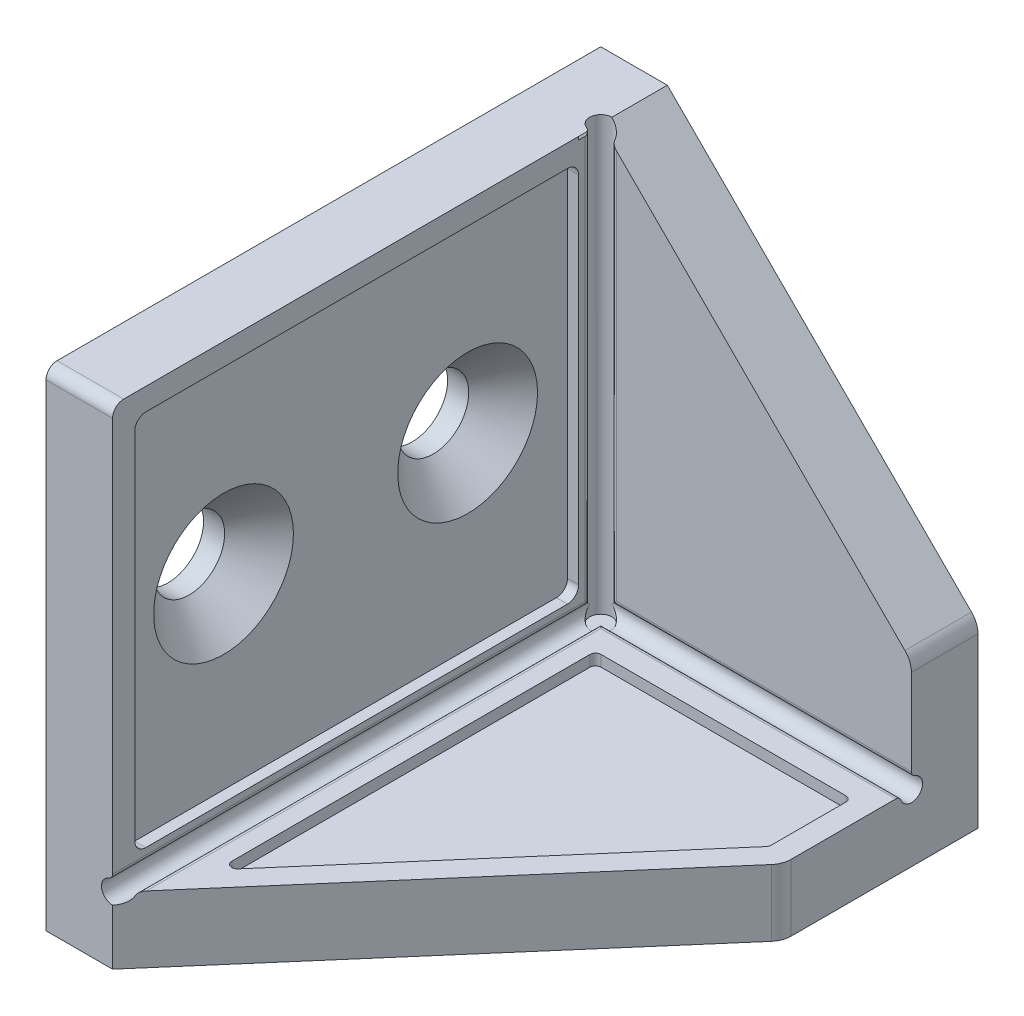
SolidWorks part; units mm, degrees
material "Polyester Resin"
ref_plane "Front Plane" through (0, 0, 0) normal (0, 0, 1) x (1, 0, 0)
ref_plane "Top Plane" through (0, 0, 0) normal (0, 1, 0) x (1, 0, 0)
ref_plane "Right Plane" through (0, 0, 0) normal (1, 0, 0) x (0, 0, -1)
sketch "Sketch1" plane through (0, 0, 0) normal (0, 0, 1) x (1, 0, 0)
  line L0 (0, 24.3075) -> (0, -0.6925)
  line L1 (0, -0.6925) -> (25, -0.6925)
  line L2 (0, 24.3075) -> (25, -0.6925)
  dimension "D1" = 25
  dimension "D2" = 25
extrude "Boss-Extrude2" add sketch "Sketch1" along normal blind 25
sketch "Sketch2" plane through (0, 0, 25) normal (0, 0, 1) x (1, 0, 0)
  line L0 (3, 21.3075) -> (3, 2.3075)
  line L1 (25, -0.6925) -> (0, 24.3075) construction
  line L2 (3, 2.3075) -> (22, 2.3075)
  line L3 (0, 24.3075) -> (0, -0.6925) construction
  line L4 (0, -0.6925) -> (25, -0.6925) construction
  line L5 (3, 21.3075) -> (22, 2.3075)
  dimension "D1" = 3
  dimension "D2" = 3
extrude "Cut-Extrude1" cut sketch "Sketch2" against normal blind 21
sketch "Sketch3" plane through (12.1537, 12.1537, 0) normal (0.7071, 0.7071, 0) x (0.7071, -0.7071, 0)
  line L0 (-12.9453, -4) -> (13.9247, -4)
  line L4 (13.9247, -4) -> (13.9247, -3)
  line L5 (13.9247, -3) -> (-12.9453, -3)
  line L6 (-12.9453, -3) -> (-12.9453, -4)
extrude "Cut-Extrude3" cut sketch "Sketch3" against normal blind 0.1
sketch "Sketch4" plane through (0, 0, 4) normal (0, 0, 1) x (1, 0, 0)
  line L0 (3, 21.3075) -> (3, 2.3075)
  line L1 (3, 2.3075) -> (22, 2.3075)
  line L2 (22, 2.3075) -> (3, 21.3075)
extrude "Cut-Extrude4" cut sketch "Sketch4" against normal up to surface (1 mm away) up to face at (12.4646, 11.7721, 3)
sketch "Sketch5" plane through (0, 0, 3) normal (0, 0, 1) x (1, 0, 0)
  line L0 (22, 2.3075) -> (21.8586, 2.3075)
  line L1 (21.8586, 2.3075) -> (21.9293, 2.2368)
  line L2 (21.9293, 2.2368) -> (22, 2.3075)
extrude "Boss-Extrude3" add sketch "Sketch5" along normal up to surface (1 mm away) up to face at (21.9293, 2.2839, 4)
sketch "Sketch6" plane through (0, 2.3075, 0) normal (0, 1, 0) x (1, 0, 0)
  line L0 (22, -3) -> (3, -3) construction
  line L1 (3, -3) -> (3, -25) construction
  line L2 (3, -25) -> (22, -25)
  point P4 (0, 0)
sketch "Sketch8" plane through (3, 0, 0) normal (1, 0, 0) x (0, 0, -1)
  line L0 (-25, 2.3075) -> (-25, 21.3075) construction
  line L1 (-25, 21.3075) -> (-3, 21.3075) construction
  line L2 (-25, 21.3075) -> (-14, 21.3075)
  line L3 (-14, 21.3075) -> (-3, 21.3075)
  line L4 (-3, 21.3075) -> (-3, 11.7368)
  line L5 (-3, 21.166) -> (-3, 2.3075) construction
  line L6 (-3, 11.7368) -> (-3, 2.3075)
  circle A0 centre (-8.5, 11.7368) radius 1.5
  circle A1 centre (-19.5, 11.7368) radius 1.5
  dimension "D1" = 3
  dimension "D2" = 3
extrude "Cut-Extrude5" cut sketch "Sketch8" against normal blind 18 and the other way blind 15 contours A0 | A1 region at (3, 11.7368, 8.5) region at (3, 11.7368, 19.5)
sketch "Sketch9" plane through (3, 0, 0) normal (1, 0, 0) x (0, 0, -1)
  circle A0 centre (-19.5, 11.7368) radius 3
  circle A1 centre (-8.5, 11.7368) radius 3
  dimension "D1" = 6
  dimension "D2" = 6
sketch "Sketch10" plane through (3, 0, 0) normal (1, 0, 0) x (0, 0, -1)
  line L0 (-25, 21.3075) -> (-25, 2.3075) construction
  line L1 (-24, 20.3075) -> (-4, 20.3075)
  line L2 (-24, 20.3075) -> (-24, 3.3075)
  line L3 (-24, 3.3075) -> (-4, 3.3075)
  line L4 (-4, 20.3075) -> (-4, 3.3075)
  line L5 (-4, 21.3075) -> (-25, 21.3075) construction
  line L6 (-3, 2.3075) -> (-25, 2.3075) construction
  line L7 (-3, 21.166) -> (-3, 2.3075) construction
  dimension "D1" = 1
  dimension "D2" = 1
  dimension "D3" = 1
  dimension "D4" = 1
extrude "Cut-Extrude7" cut sketch "Sketch10" against normal blind 0.5
sketch "Sketch12" plane through (0, 0, 25) normal (0, 0, 1) x (1, 0, 0)
  line L0 (3, 21.3075) -> (0, 21.3075)
  line L1 (0, 24.3075) -> (0, -0.6925) construction
  line L2 (0, 21.3075) -> (0, 24.3075)
  line L3 (0, 24.3075) -> (3, 21.3075)
  line L4 (22, 2.3075) -> (22, -0.6925)
  line L5 (0, -0.6925) -> (25, -0.6925) construction
  line L6 (22, -0.6925) -> (25, -0.6925)
  line L7 (25, -0.6925) -> (22, 2.3075)
extrude "Cut-Extrude9" cut sketch "Sketch12" against normal through all
fillet "Fillet1" radius 0.5 1 edges at (1.5, 21.3075, 25)
fillet "Fillet2" radius 0.5 1 edges at (2.75, 20.3075, 24)
fillet "Fillet3" radius 0.5 3 edges at (2.75, 3.3075, 24) (2.75, 3.3075, 4) (2.75, 20.3075, 4)
sketch "Sketch13" plane through (0, 2.3075, 0) normal (0, 1, 0) x (1, 0, 0)
  line L0 (22, -3) -> (3, -25)
  line L1 (3, -25) -> (22, -25)
  line L2 (22, -25) -> (22, -3)
extrude "Cut-Extrude10" cut sketch "Sketch13" against normal through all
sketch "Sketch14" plane through (0, -0.6925, 0) normal (0, -1, 0) x (1, 0, 0)
  line L0 (22, 3) -> (3, 25) construction
  line L1 (22, 0) -> (17, 0)
  line L2 (22, 0) -> (22, 8.7895)
  line L3 (22, 8.7895) -> (17, 8.7895)
  line L4 (17, 0) -> (17, 8.7895)
  dimension "D1" = 5
extrude "Cut-Extrude11" cut sketch "Sketch14" against normal through all
sketch "Sketch15" plane through (0, -0.6925, 0) normal (0, -1, 0) x (1, 0, 0)
  line L0 (1, 24) -> (2.5423, 24)
  line L1 (2.5423, 24) -> (9.2712, 16.2087)
  line L2 (16, 8.4174) -> (16, 1)
  line L3 (16, 1) -> (1, 1)
  line L4 (1, 1) -> (1, 7.7441)
  line L5 (17, 8.7895) -> (3, 25) construction
  line L6 (0, 25) -> (0, 0) construction
  line L7 (0, 0) -> (17, 0) construction
  line L8 (17, 8.7895) -> (17, 0) construction
  line L9 (0, 25) -> (3, 25) construction
  line L10 (9.2712, 16.2087) -> (1, 9.0654)
  line L12 (1, 7.7441) -> (9.9248, 15.4519)
  line L13 (9.9248, 15.4519) -> (16, 8.4174)
  line L14 (1, 9.0654) -> (1, 24)
  dimension "D1" = 1
  dimension "D2" = 1
  dimension "D3" = 1
  dimension "D4" = 1
  dimension "D5" = 1
  dimension "D6" = 1
extrude "Cut-Extrude12" cut sketch "Sketch15" against normal blind 0.5
fillet "Fillet5" radius 0.5 9 edges at (1, -0.4425, 7.7441) (1, -0.4425, 1) (16, -0.4425, 1) (16, -0.4425, 8.4174) (2.5423, -0.4425, 24) (1, -0.4425, 24) (1, -0.4425, 9.0654) (9.2712, -0.4425, 16.2087) (9.9248, -0.4425, 15.4519)
sketch "Sketch16" plane through (0, 0, 0) normal (0, 0, -1) x (-1, 0, 0)
  line L0 (-1, 0.3075) -> (-1, 3.8933)
  line L1 (-1, 20.3075) -> (-2.5858, 20.3075)
  line L2 (-2.5858, 20.3075) -> (-9.2929, 13.6004)
  line L3 (-16, 6.8933) -> (-16, 0.3075)
  line L4 (-16, 0.3075) -> (-1, 0.3075)
  line L5 (-17, 7.3075) -> (-3, 21.3075) construction
  line L6 (0, 21.3075) -> (0, -0.6925) construction
  line L7 (0, -0.6925) -> (-17, -0.6925) construction
  line L8 (-17, 7.3075) -> (-17, -0.6925) construction
  line L9 (0, 21.3075) -> (-3, 21.3075) construction
  line L10 (-9.2929, 13.6004) -> (-1, 5.3075)
  line L12 (-1, 3.8933) -> (-10, 12.8933)
  line L13 (-10, 12.8933) -> (-16, 6.8933)
  line L14 (-1, 5.3075) -> (-1, 20.3075)
  point P19 (-5.1464, 9.4539)
  dimension "D1" = 1
  dimension "D2" = 1
  dimension "D3" = 1
  dimension "D4" = 1
  dimension "D5" = 1
  dimension "D6" = 1
extrude "Cut-Extrude13" cut sketch "Sketch16" against normal blind 0.5
fillet "Fillet7" radius 0.25 9 edges at (1, 3.8933, 0.25) (1, 20.3075, 0.25) (16, 6.8933, 0.25) (16, 0.3075, 0.25) (1, 0.3075, 0.25) (1, 5.3075, 0.25) (9.2929, 13.6004, 0.25) (2.5858, 20.3075, 0.25) (10, 12.8933, 0.25)
fillet "Fillet10" radius 1 2 edges at (17, 0.8075, 8.7895) (17, 7.3075, 1.5)
hole_wizard "CSK for M3 Flat Head Machine Screw1" positions "Sketch17" profile "Sketch18" countersink size "M3" standard "ANSI Metric" end condition through all
sketch "Sketch17" plane through (2.5, 0, 0) normal (1, 0, 0) x (0, 0, -1)
  point P0 (-19.5, 11.7368)
  point P3 (-8.5, 11.7368)
sketch "Sketch18" plane through (2.5, 11.7368, 19.5) normal (0, 1, 0) x (0, 0, -1)
  line L0 (0, 0) -> (0, 2.5)
  line L1 (0, 2.5) -> (1.6, 2.5)
  line L2 (1.6, 2.5) -> (1.6, 1.55)
  line L3 (1.6, 1.55) -> (3.15, 0)
  line L5 (3.15, 0) -> (0, 0)
  line L6 (-1.6, 1.55) -> (-3.15, 0) construction
  line L11 (0, -6.35) -> (0, 107.95) construction
  dimension "Thru Hole Dia." = 3.2
  dimension "Thru Hole Depth" = 2.5
  dimension "Near C'Sink Dia." = 6.3
  dimension "Near C'Sink Angle" = 90
sketch "Sketch19" plane through (17, 0, 0) normal (1, 0, 0) x (0, 0, -1)
  circle A0 centre (-3, 2.3075) radius 0.5
  dimension "D1" = 1
extrude "Cut-Extrude14" cut sketch "Sketch19" against normal blind 14
sketch "Sketch20" plane through (0, 0, 25) normal (0, 0, 1) x (1, 0, 0)
  circle A0 centre (3, 2.3075) radius 0.5
  dimension "D1" = 1
extrude "Cut-Extrude15" cut sketch "Sketch20" against normal blind 22
sketch "Sketch21" plane through (0, 21.3075, 0) normal (0, 1, 0) x (1, 0, 0)
  circle A0 centre (3, -3) radius 0.5
  dimension "D1" = 1
extrude "Cut-Extrude16" cut sketch "Sketch21" against normal blind 19.5
fillet "Fillet11" radius 0.25 6 edges at (3, 11.9868, 3.5) (3, 2.8075, 14.25) (3.5, 11.8075, 3) (10.25, 2.8075, 3) (10.25, 2.3075, 3.5) (3.5, 2.3075, 13.9605)
sketch "Sketch22" plane through (0, 2.3075, 0) normal (0, 1, 0) x (1, 0, 0)
  line L0 (4.4714, -21.7663) -> (16, -8.4174)
  line L1 (4.4714, -4.7071) -> (16, -4.7071)
  line L2 (4.4714, -4.7071) -> (4.4714, -21.7663)
  line L4 (16, -4.7071) -> (16, -8.4174)
  line L5 (16.7568, -9.071) -> (3.7071, -24.1812) construction
  line L6 (17, -8.4174) -> (17, -3.7071) construction
  line L7 (17, -3.7071) -> (3.7071, -3.7071) construction
  line L8 (3.4714, -24.4542) -> (3.4714, -3.4714) construction
  dimension "D1" = 1
  dimension "D2" = 1
  dimension "D3" = 1
  dimension "D4" = 1
extrude "Cut-Extrude17" cut sketch "Sketch22" against normal blind 0.5
fillet "Fillet12" radius 0.25 3 edges at (16, 2.0575, 8.4174) (16, 2.0575, 4.7071) (4.4714, 2.0575, 4.7071)
fillet "Fillet13" radius 0.25 1 edges at (4.4714, 2.0575, 21.7663)
